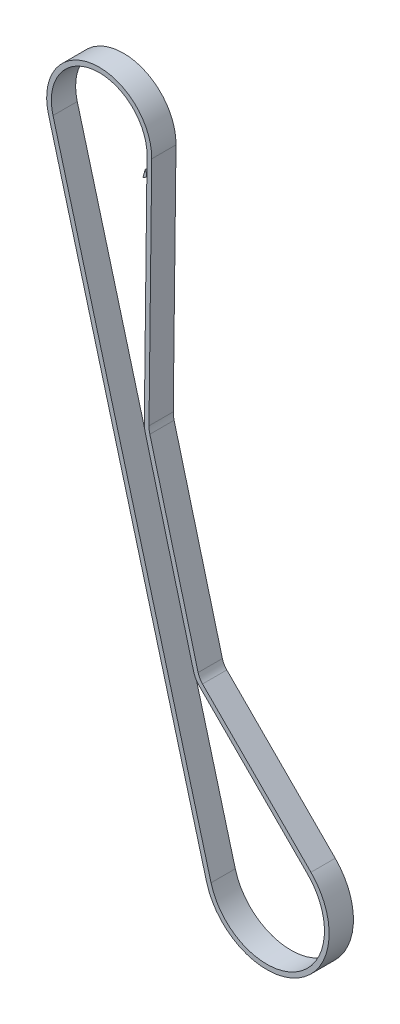
SolidWorks part; units mm, degrees
ref_plane "Front Plane" through (0, 0, 0) normal (0, 0, 1) x (1, 0, 0)
ref_plane "Top Plane" through (0, 0, 0) normal (0, 1, 0) x (1, 0, 0)
ref_plane "Right Plane" through (0, 0, 0) normal (1, 0, 0) x (0, 0, -1)
sketch "Sketch2" plane through (0, 0, 0) normal (0, 0, 1) x (1, 0, 0)
  line L0 (0, 0) -> (1, 0) construction
  line L1 (0, 0) -> (0, 1) construction
  line L13 (48.172, -235.8177) -> (-10.4521, -18.6201)
  line L20 (45.2426, -173.9057) -> (85.4692, -214.2862)
  line L22 (26.1433, -13.9871) -> (25.1274, -100.278)
  line L23 (25.4733, -103.062) -> (43.3784, -170.6588)
  arc A4 (85.4692, -214.2862) -> (48.172, -235.8177) centre (69.6837, -230.0114) cw
  arc A7 (-10.4521, -18.6201) -> (26.1433, -13.9871) centre (7.5246, -13.768) cw
  arc A8 (43.3784, -170.6588) -> (45.2426, -173.9057) centre (50.3577, -168.8101) ccw
  arc A11 (25.1274, -100.278) -> (25.4733, -103.062) centre (35.5217, -100.4004) ccw
extrude "Extrude-Thin1" add sketch "Sketch2" along normal blind 9 thin thin type two direction wall 0.87 second wall 0.87
sketch "Sketch3" plane through (0, 0, 0) normal (0, 0, -1) x (-1, 0, 0)
  line L0 (-24.5995, -18.6166) -> (-23.6893, -21.8219)
  line L1 (9.6122, -18.3934) -> (-49.012, -235.591) construction
  line L3 (-24.5995, -18.6166) -> (-28.0198, -6.572) construction
  arc A0 (-24.6966, -19.0251) -> (-23.9866, -21.5254) centre (-23.574, -20.0572) ccw
  arc A1 (-24.5995, -18.6166) -> (-24.6966, -19.0251) centre (-25.0132, -18.7341) cw
  arc A2 (-23.6893, -21.8219) -> (-23.9866, -21.5254) centre (-24.103, -21.9393) ccw
  point P2 (-22.049, -20.0572)
  dimension "D1" = 3.05
  dimension "D3" = 0.43
  dimension "D2" = 2.06
extrude "Boss-Extrude1" add sketch "Sketch3" against normal up to surface (9 mm away) up to face at (37.8775, -129.0936, 9)
pattern_curve "CrvPattern1" rebuild error yes driven by "Sketch2" parameters "D1"=119, "D3"=5, "D2"=1, "D4"=50
